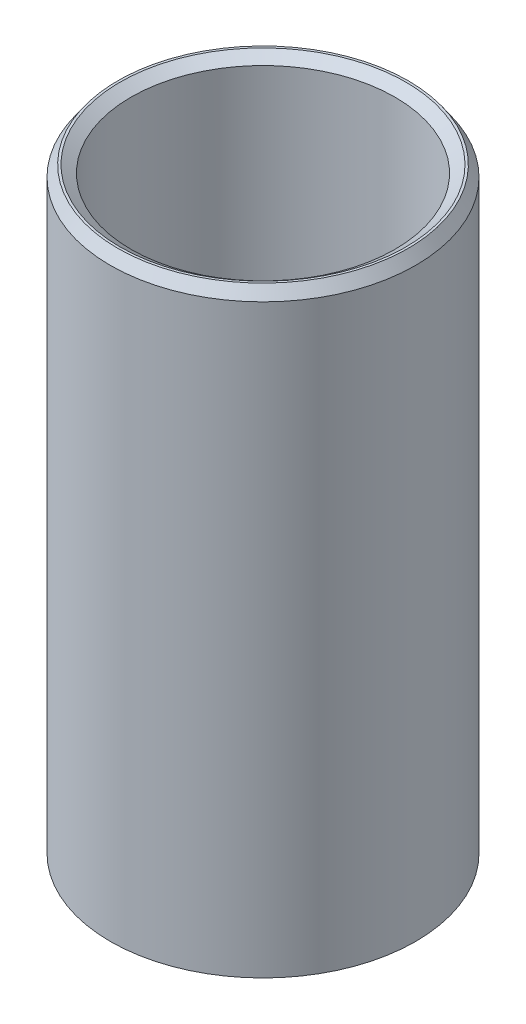
SolidWorks part; units mm, degrees
ref_plane "Front Plane" through (0, 0, 0) normal (0, 0, 1) x (1, 0, 0)
ref_plane "Top Plane" through (0, 0, 0) normal (0, 1, 0) x (1, 0, 0)
ref_plane "Right Plane" through (0, 0, 0) normal (1, 0, 0) x (0, 0, -1)
sketch "Sketch1" plane through (0, 0, 0) normal (0, 1, 0) x (1, 0, 0)
  circle A0 centre (0, 0) radius 55
  dimension "SLEEVE_OD" = 110
extrude "Boss-Extrude1" add sketch "Sketch1" along normal blind 217.4901
sketch "Sketch2" plane through (0, 0, 0) normal (0, 1, 0) x (1, 0, 0)
  circle A0 centre (0, 0) radius 47.5055
  dimension "BORE_D" = 95.011
extrude "Cut-Extrude1" cut sketch "Sketch2" along normal through all
chamfer "Chamfer1" distance 3.9389 angle 34.52 4 edges at (0, 217.4901, 47.5055) (0, 0, 47.5055) (0, 0, 55) (0, 217.4901, 55) first distance on face at (0, 217.4901, 47.5055) first distance on face at (0, 0, 47.5055) first distance on face at (0, 217.4901, 55)
